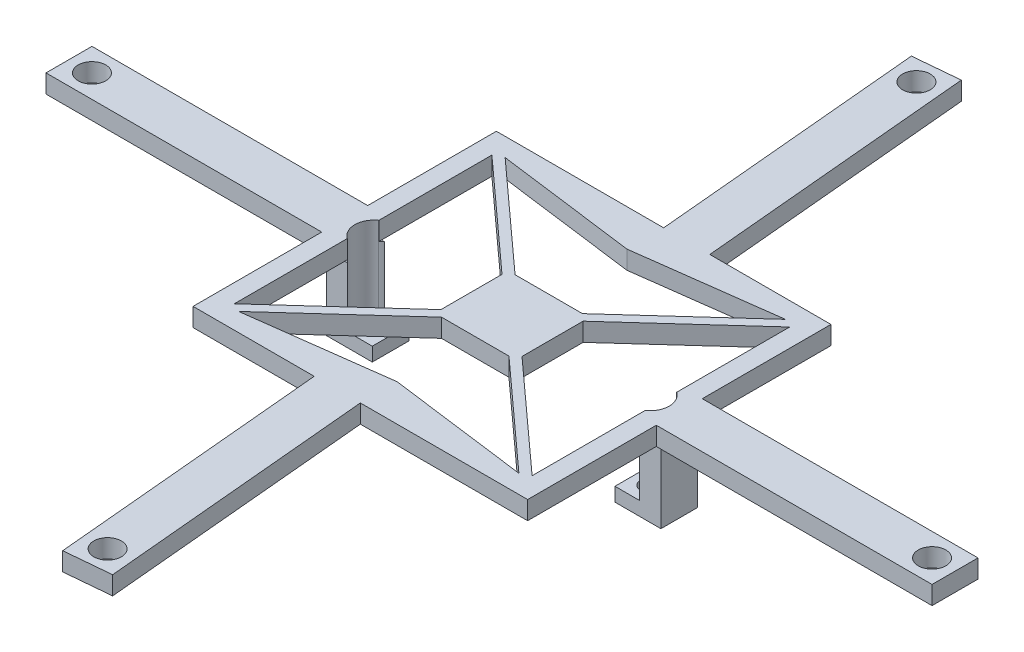
SolidWorks part; units mm, degrees
ref_plane "Front Plane" through (0, 0, 0) normal (0, 0, 1) x (1, 0, 0)
ref_plane "Top Plane" through (0, 0, 0) normal (0, 1, 0) x (1, 0, 0)
ref_plane "Right Plane" through (0, 0, 0) normal (1, 0, 0) x (0, 0, -1)
sketch "Sketch1" plane through (0, 0, 0) normal (0, 1, 0) x (1, 0, 0)
  line L0 (-17.8642, 16.8704) -> (18.5358, -16.1296) construction
  line L1 (-18.2, -16.5) -> (18.2, -16.5)
  line L2 (-18.2, -16.5) -> (-18.2, 16.5)
  line L3 (-18.2, 16.5) -> (18.2, 16.5)
  line L4 (18.2, -16.5) -> (18.2, 16.5)
  line L5 (-18.2, -16.5) -> (18.2, 16.5) construction
  line L6 (-18.2, 16.5) -> (18.2, -16.5) construction
  line L7 (-15.2495, -14.5) -> (15.2495, -14.5) construction
  line L8 (-16.2, -14.0119) -> (-16.2, 14.0119)
  line L9 (-15.2495, 14.5) -> (15.2495, 14.5) construction
  line L10 (16.2, -14.0119) -> (16.2, 14.0119)
  line L11 (-16.6417, -15.0873) -> (17.1872, 15.5818) construction
  line L12 (0, 14.5) -> (0, 12.5) construction
  line L13 (-15.2495, 14.5) -> (-3.6677, 4)
  line L14 (-16.2, 14.0119) -> (-4.4121, 3.3251)
  line L15 (-15.2495, -14.5) -> (-3.6677, -4)
  line L16 (-16.2, -14.0119) -> (-4.4121, -3.3251)
  line L17 (-17.8642, -16.8704) -> (18.5358, 16.1296) construction
  line L18 (-18.5358, -16.1296) -> (17.8642, 16.8704) construction
  line L19 (3.6677, -4) -> (15.2495, -14.5)
  line L20 (3.6677, 4) -> (15.2495, 14.5)
  line L21 (4.4121, 3.3251) -> (16.2, 14.0119)
  line L22 (4.4121, -3.3251) -> (16.2, -14.0119)
  line L23 (-15.2495, 14.5) -> (0, 12.5)
  line L24 (-4.4121, -4) -> (4.4121, -4)
  line L25 (-4.4121, -4) -> (-4.4121, 4)
  line L26 (-4.4121, 4) -> (4.4121, 4)
  line L27 (4.4121, -4) -> (4.4121, 4)
  line L28 (-4.4121, -4) -> (4.4121, 4) construction
  line L29 (-4.4121, 4) -> (4.4121, -4) construction
  line L30 (0, 12.5) -> (15.2495, 14.5)
  line L31 (0, 0) -> (2.0517, 0) construction
  line L32 (0, -14.5) -> (0, -12.5) construction
  line L33 (-15.2495, -14.5) -> (0, -12.5)
  line L34 (0, -12.5) -> (15.2495, -14.5)
  point P0 (0, 0)
  point P6 (0, 0)
  point P24 (0, 0)
  dimension "D1" = 36.4
  dimension "D2" = 33
  dimension "D3" = 2
  dimension "D7" = 2
  dimension "D8" = 2
  dimension "D9" = 2
  dimension "D10" = 0.5
  dimension "D11" = 8
  dimension "D12" = 2
  dimension "D4" = 0.5
  dimension "D5" = 0.5
  dimension "D6" = 0.5
extrude "Boss-Extrude1" add sketch "Sketch1" along normal blind 2 contours L1 L4 L3 L2 L22 L21 L10 L15 L16 L8 L14 L13 L9 L20 L19 L7 | L24 L27 L26 L25 region at (-17.7087, 0, 0) region at (0, 0, 0)
sketch "Sketch2" plane through (0, 0, 0) normal (0, -1, 0) x (1, 0, 0)
  line L0 (0, 0) -> (8.5389, 0) construction
  line L1 (18.2, 2) -> (13.2, 2)
  line L7 (-18.2, -16.5) -> (-18.2, 16.5) construction
  line L8 (-18.2, -2) -> (-13.2, -2)
  line L9 (0, 0) -> (0, 9.5432) construction
  line L10 (-18.2, -2) -> (-18.2, 2)
  line L11 (-18.2, 2) -> (-13.2, 2)
  line L12 (-13.2, -2) -> (-13.2, 2)
  line L13 (13.2, -2) -> (13.2, 2)
  line L14 (18.2, -2) -> (13.2, -2)
  line L15 (18.2, -2) -> (18.2, 2)
  point P2 (-13.2, 0)
  dimension "D1" = 5
  dimension "D2" = 4
extrude "Boss-Extrude2" add sketch "Sketch2" along normal blind 8
sketch "Sketch4" plane through (0, 1, 0) normal (0, 1, 0) x (1, 0, 0)
  line L0 (-15, 0) -> (15, 0) construction
  line L1 (0, 0) -> (0, 8.9985) construction
  circle A0 centre (15, 0) radius 1
  circle A1 centre (-15, 0) radius 1
  point P7 (0, 0)
  dimension "D2" = 2
  dimension "D1" = 15
extrude "Cut-Extrude2" cut sketch "Sketch4" against normal through all
sketch "Sketch3" plane through (0, 2, 0) normal (0, 1, 0) x (1, 0, 0)
  line L0 (0, 0) -> (15, 0) construction
  line L1 (15, 4.1243) -> (15, 4.258)
  line L2 (15, 4.258) -> (10.3222, 4.258)
  line L3 (10.3222, 4.258) -> (10.3222, -5.2397)
  line L4 (10.3222, -5.2397) -> (15, -5.2397)
  line L5 (15, -5.2397) -> (15, -4.1243)
  line L6 (0, 0) -> (0, 10.8367) construction
  line L7 (-10.3222, -5.2397) -> (-15, -5.2397)
  line L8 (-10.3222, 4.258) -> (-10.3222, -5.2397)
  line L9 (-15, 4.258) -> (-10.3222, 4.258)
  line L10 (-15, 4.1243) -> (-15, 4.258)
  line L11 (-15, -5.2397) -> (-15, -4.1243)
  arc A0 (16.2353, -1.6982) -> (16.2353, 1.6982) centre (15, 0) ccw
  arc A1 (-16.2353, -1.6982) -> (-16.2353, 1.6982) centre (-15, 0) cw
  arc A2 (-15, 4.1243) -> (-16.2353, 1.6982) centre (-18, 4.1243) cw
  arc A3 (-16.2353, -1.6982) -> (-15, -4.1243) centre (-18, -4.1243) cw
  arc A4 (15, 4.1243) -> (16.2353, 1.6982) centre (18, 4.1243) ccw
  arc A5 (15, -4.1243) -> (16.2353, -1.6982) centre (18, -4.1243) cw
  point P20 (-15, 2.1)
  point P23 (-15, -2.1)
  point P26 (15, 2.1)
  point P29 (15, -2.1)
  dimension "D2" = 4.2
  dimension "D3" = 3
  dimension "D4" = 3
  dimension "D1" = 15
extrude "Cut-Extrude1" cut sketch "Sketch3" against normal blind 8.5
sketch "Sketch5" plane through (-18.2, 0, 0) normal (-1, 0, 0) x (0, 0, 1)
  line L0 (0, 0) -> (0, 2)
  line L1 (16.5, 2) -> (-16.5, 2) construction
  line L3 (-2.5, 2) -> (2.5, 2)
  line L4 (-2.5, 2) -> (-2.5, 0)
  line L5 (-2.5, 0) -> (2.5, 0)
  line L6 (2.5, 2) -> (2.5, 0)
  line L7 (-2.5, 2) -> (2.5, 0) construction
  line L8 (-2.5, 0) -> (2.5, 2) construction
  point P5 (0, 1)
  line M8 (16.5, 2) -> (-16.5, 2)
  dimension "D1" = 5
extrude "Boss-Extrude3" add sketch "Sketch5" along normal blind 30 contours L6 L0 L5 M8 | L4 L5 L0 M8 region at (-18.2, 1, -1.25) region at (-18.2, 1, 1.25)
sketch "Sketch6" plane through (18.2, 0, 0) normal (1, 0, 0) x (0, 0, -1)
  line L0 (0, 0) -> (0, 2)
  line L1 (-16.5, 2) -> (16.5, 2) construction
  line L3 (-2.5, 2) -> (2.5, 2)
  line L4 (-2.5, 2) -> (-2.5, 0)
  line L5 (-2.5, 0) -> (2.5, 0)
  line L6 (2.5, 2) -> (2.5, 0)
  line L7 (-2.5, 2) -> (2.5, 0) construction
  line L8 (-2.5, 0) -> (2.5, 2) construction
  point P5 (0, 1)
  line M11 (16.5, 2) -> (-16.5, 2)
  dimension "D1" = 5
extrude "Boss-Extrude4" add sketch "Sketch6" along normal blind 30 contours L4 L5 L0 M11 | L6 L0 L5 M11 region at (18.2, 1, 1.25) region at (18.2, 1, -1.25)
sketch "Sketch11" plane through (0, 2, 0) normal (0, 1, 0) x (1, 0, 0)
  line L0 (-48.2, 2.5) -> (-18.2, 2.5) construction
  line L1 (-48.2, -2.5) -> (-43.2, -2.5) construction
  line L2 (-48.2, -2.5) -> (-48.2, 2.5) construction
  line L3 (-48.2, 2.5) -> (-43.2, 2.5) construction
  line L4 (-43.2, -2.5) -> (-43.2, 2.5) construction
  line L5 (-43.2, -2.5) -> (-48.2, 2.5) construction
  line L6 (0, 0) -> (0, 7.9633) construction
  circle A0 centre (-45.7, 0) radius 1.5
  circle A1 centre (45.7, 0) radius 1.5
  dimension "D1" = 3
extrude "Cut-Extrude3" cut sketch "Sketch11" against normal through all contours A0 | A1
sketch "Sketch10" plane through (0, 2, 0) normal (0, 1, 0) x (1, 0, 0)
  line L0 (0, 0) -> (0, 6.2456) construction
  line L1 (-5.0208, -16.5) -> (-2.2718, -46.614)
  line L2 (-18.2, -16.5) -> (18.2, -16.5) construction
  line L3 (0, -16.5) -> (2.7075, -46.1594)
  line L5 (-2.2718, -46.614) -> (2.7075, -46.1594)
  line L8 (-2.2718, -46.614) -> (2.2718, -41.386) construction
  line L9 (2.7075, -46.1594) -> (-2.7075, -41.8406) construction
  line L10 (-2.7075, -41.8406) -> (2.2718, -41.386) construction
  line L12 (-5.0208, -16.5) -> (0, -16.5)
  line L14 (5.0208, 16.5) -> (0, 16.5)
  line L15 (2.7075, 41.8406) -> (-2.2718, 41.386) construction
  line L16 (-2.7075, 46.1594) -> (2.7075, 41.8406) construction
  line L17 (0, 16.5) -> (-2.7075, 46.1594)
  line L18 (2.2718, 46.614) -> (-2.7075, 46.1594)
  line L19 (2.2718, 46.614) -> (-2.2718, 41.386) construction
  line L20 (5.0208, 16.5) -> (2.2718, 46.614)
  circle A2 centre (0, -44) radius 1.5
  circle A3 centre (0, 44) radius 1.5
  point P9 (0, -44)
  point P15 (0, 16.5)
  point P21 (0, 44)
  line M25 (-18.2, -16.5) -> (18.2, -16.5)
  line M31 (18.2, 16.5) -> (-18.2, 16.5)
  dimension "D1" = 5
  dimension "D2" = 27.5
  dimension "D3" = 3
  dimension "D5" = 3
  dimension "D4" = 5
extrude "Boss-Extrude5" add sketch "Sketch10" against normal blind 2 contours L1 L5 L3 A2 M25 | L20 L18 L17 A3 M31 region at (-1.2096, 2, 30.8229) region at (1.2096, 2, -30.8229)
sketch "Sketch7" plane through (0, 2, 0) normal (0, 1, 0) x (1, 0, 0)
  line L0 (0, -12.5) -> (0, -13.5)
  line L1 (0, -13.5) -> (3, -13.5)
  line L2 (3, -13.5) -> (3, -14.5)
  line L3 (3, -14.5) -> (-3, -14.5)
  line L4 (-3, -14.5) -> (-3, -15.5)
  line L5 (-3, -15.5) -> (0, -15.5)
  line L6 (0, -15.5) -> (0, -16.5)
  line L8 (0, 0) -> (8.7368, 0) construction
  line L9 (0, 15.5) -> (0, 16.5)
  line L10 (-3, 15.5) -> (0, 15.5)
  line L11 (-3, 14.5) -> (-3, 15.5)
  line L12 (3, 14.5) -> (-3, 14.5)
  line L13 (3, 13.5) -> (3, 14.5)
  line L14 (0, 13.5) -> (3, 13.5)
  line L15 (0, 12.5) -> (0, 13.5)
  line L16 (-4.4121, 0) -> (-3, 0) construction
  line L17 (3, 0) -> (3, -4)
  line L18 (-4.4121, -3.3251) -> (-4.4121, 3.3251) construction
  line L19 (-3, 0) -> (-3, -3)
  line L20 (-3, -3) -> (-2, -3)
  line L21 (-2, -3) -> (-2, 3)
  line L22 (-2, 3) -> (-1, 3)
  line L23 (-1, 3) -> (-1, -3)
  line L24 (-1, -3) -> (0, -3)
  line L25 (0, -3) -> (0, 3)
  line L26 (0, 3) -> (1, 3)
  line L27 (1, 3) -> (1, -3)
  line L28 (1, -3) -> (2, -3)
  line L29 (2, -3) -> (2, 3)
  line L30 (2, 3) -> (3, 3)
  line L31 (3, 3) -> (3, 0)
  line L32 (3, 0) -> (4.4121, 0) construction
  line L33 (4.4121, -3.3251) -> (4.4121, 3.3251) construction
  line L34 (-3.6677, -4) -> (3.6677, -4) construction
  line L35 (-3, 0) -> (-3, 4)
  line L36 (-3.6677, 4) -> (3.6677, 4) construction
  dimension "D1" = 3
  dimension "D2" = 1
  dimension "D3" = 1
  dimension "D4" = 6
